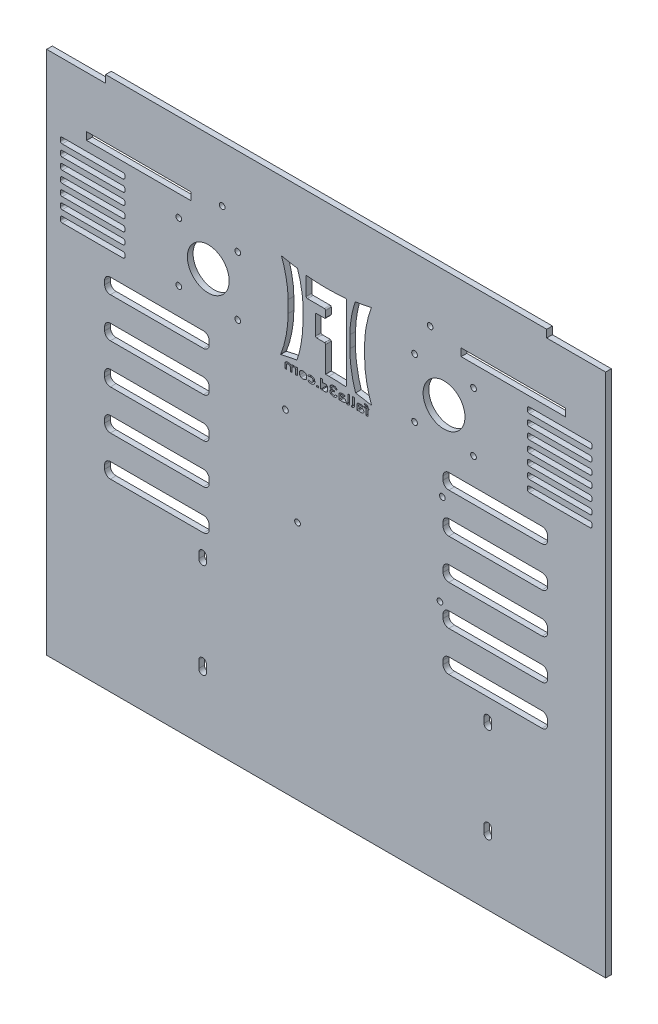
SolidWorks part; units mm, degrees
ref_plane "Front Plane" through (0, 0, 0) normal (0, 0, 1) x (1, 0, 0)
ref_plane "Top Plane" through (0, 0, 0) normal (0, 1, 0) x (1, 0, 0)
ref_plane "Right Plane" through (0, 0, 0) normal (1, 0, 0) x (0, 0, -1)
sketch "Sketch1" plane through (0, 0, 0) normal (0, 0, 1) x (1, 0, 0)
  line L0 (-46.5, 81) -> (-77.5, 81) construction
  line L1 (147, -122) -> (-147, -122)
  line L2 (147, -122) -> (147, 122)
  line L3 (147, 122) -> (-147, 122)
  line L4 (-147, -122) -> (-147, 122)
  line L5 (147, -122) -> (-147, 122) construction
  line L6 (147, 122) -> (-147, -122) construction
  line L7 (-46.5, 81) -> (-46.5, 112) construction
  line L8 (-46.5, 112) -> (-77.5, 112) construction
  line L9 (-77.5, 81) -> (-77.5, 112) construction
  line L10 (-46.5, 81) -> (-77.5, 112) construction
  line L11 (-46.5, 112) -> (-77.5, 81) construction
  line L12 (0, 122) -> (0, -133.2191) construction
  line L13 (46.5, 112) -> (77.5, 81) construction
  line L14 (46.5, 81) -> (77.5, 112) construction
  line L15 (77.5, 81) -> (77.5, 112) construction
  line L16 (46.5, 112) -> (77.5, 112) construction
  line L17 (46.5, 81) -> (46.5, 112) construction
  line L18 (46.5, 81) -> (77.5, 81) construction
  line L19 (-175.5662, 128.75) -> (218.0802, 128.75) construction
  line L20 (-147, 122) -> (147, 122)
  line L21 (-147, 122) -> (-147, 158)
  line L22 (-147, 158) -> (147, 158)
  line L23 (147, 122) -> (147, 158)
  line L24 (0, 158) -> (0, 122) construction
  line L25 (-147, 140) -> (147, 140) construction
  line L26 (147, 156) -> (116, 156) construction
  line L27 (-147, 158) -> (-116, 158)
  line L28 (-147, 158) -> (-147, 154)
  line L29 (-147, 154) -> (-116, 154)
  line L30 (-116, 158) -> (-116, 154)
  line L31 (-131.5, 154) -> (-131.5, 158) construction
  line L32 (-147, 156) -> (-116, 156) construction
  line L33 (131.5, 154) -> (131.5, 158) construction
  line L34 (116, 158) -> (116, 154)
  line L35 (147, 154) -> (116, 154)
  line L36 (147, 158) -> (147, 154)
  line L37 (147, 158) -> (116, 158)
  line L38 (-65, -38) -> (-65, -35.0783) construction
  line L39 (-67, -38) -> (-67, -35.0783)
  line L40 (-63, -38) -> (-63, -35.0783)
  line L41 (-65, -88) -> (-65, -84.0783) construction
  line L42 (-67, -88) -> (-67, -84.0783)
  line L43 (-63, -88) -> (-63, -84.0783)
  line L44 (85, -38) -> (85, -35.0783) construction
  line L45 (83, -38) -> (83, -35.0783)
  line L46 (87, -38) -> (87, -35.0783)
  line L47 (85, -88) -> (85, -84.0783) construction
  line L48 (83, -88) -> (83, -84.0783)
  line L49 (87, -88) -> (87, -84.0783)
  line L50 (-116.5, 63) -> (-61.5, 63) construction
  line L51 (113.5, 67) -> (64.5, 67)
  line L52 (116.5, 64) -> (116.5, 62)
  line L53 (113.5, 59) -> (64.5, 59)
  line L54 (61.5, 64) -> (61.5, 62)
  line L55 (89, 59) -> (89, 67) construction
  line L56 (116.5, 63) -> (61.5, 63) construction
  line L57 (-89, 59) -> (-89, 67) construction
  line L58 (-61.5, 64) -> (-61.5, 62)
  line L59 (-113.5, 59) -> (-64.5, 59)
  line L60 (-116.5, 64) -> (-116.5, 62)
  line L61 (-113.5, 67) -> (-64.5, 67)
  line L62 (113.5, 46) -> (64.5, 46)
  line L63 (116.5, 43) -> (116.5, 41)
  line L64 (113.5, 38) -> (64.5, 38)
  line L65 (61.5, 43) -> (61.5, 41)
  line L66 (-61.5, 43) -> (-61.5, 41)
  line L67 (-113.5, 38) -> (-64.5, 38)
  line L68 (-116.5, 43) -> (-116.5, 41)
  line L69 (-113.5, 46) -> (-64.5, 46)
  line L70 (-116.5, 42) -> (-61.5, 42) construction
  line L71 (89, 38) -> (89, 46) construction
  line L72 (116.5, 42) -> (61.5, 42) construction
  line L73 (-89, 38) -> (-89, 46) construction
  line L74 (113.5, 25) -> (64.5, 25)
  line L75 (116.5, 22) -> (116.5, 20)
  line L76 (113.5, 17) -> (64.5, 17)
  line L77 (61.5, 22) -> (61.5, 20)
  line L78 (-61.5, 22) -> (-61.5, 20)
  line L79 (-113.5, 17) -> (-64.5, 17)
  line L80 (-116.5, 22) -> (-116.5, 20)
  line L81 (-113.5, 25) -> (-64.5, 25)
  line L82 (-116.5, 21) -> (-61.5, 21) construction
  line L83 (89, 17) -> (89, 25) construction
  line L84 (116.5, 21) -> (61.5, 21) construction
  line L85 (-89, 17) -> (-89, 25) construction
  line L86 (113.5, 4) -> (64.5, 4)
  line L87 (116.5, 1) -> (116.5, -1)
  line L88 (113.5, -4) -> (64.5, -4)
  line L89 (61.5, 1) -> (61.5, -1)
  line L90 (-61.5, 1) -> (-61.5, -1)
  line L91 (-113.5, -4) -> (-64.5, -4)
  line L92 (-116.5, 1) -> (-116.5, -1)
  line L93 (-113.5, 4) -> (-64.5, 4)
  line L94 (-116.5, 0) -> (-61.5, 0) construction
  line L95 (89, -4) -> (89, 4) construction
  line L96 (116.5, 0) -> (61.5, 0) construction
  line L97 (-89, -4) -> (-89, 4) construction
  line L98 (113.5, -17) -> (64.5, -17)
  line L99 (116.5, -20) -> (116.5, -22)
  line L100 (113.5, -25) -> (64.5, -25)
  line L101 (61.5, -20) -> (61.5, -22)
  line L102 (-61.5, -20) -> (-61.5, -22)
  line L103 (-113.5, -25) -> (-64.5, -25)
  line L104 (-116.5, -20) -> (-116.5, -22)
  line L105 (-113.5, -17) -> (-64.5, -17)
  line L106 (-116.5, -21) -> (-61.5, -21) construction
  line L107 (89, -25) -> (89, -17) construction
  line L108 (116.5, -21) -> (61.5, -21) construction
  line L109 (-89, -25) -> (-89, -17) construction
  line L110 (0, 79) -> (0, 82) construction
  line L111 (0, 87) -> (0, 90) construction
  line L112 (0, 95) -> (0, 98) construction
  line L113 (0, 111) -> (0, 114) construction
  line L116 (0, 103) -> (0, 106) construction
  line L117 (-15.0972, 71.2645) -> (-15.0972, 74.8635)
  line L118 (-16.0206, 71.2645) -> (-15.0972, 71.2645)
  line L119 (-16.0206, 73.4099) -> (-16.0206, 71.2645)
  line L121 (-17.937, 71.2645) -> (-17.937, 73.4099)
  line L122 (-18.8595, 71.2645) -> (-17.937, 71.2645)
  line L123 (-18.8595, 73.4099) -> (-18.8595, 71.2645)
  line L125 (-20.7714, 71.2645) -> (-20.7714, 73.4099)
  line L126 (-21.6948, 71.2645) -> (-20.7714, 71.2645)
  line L127 (-21.6948, 73.6569) -> (-21.6948, 71.2645)
  line L129 (-16.0215, 74.4822) -> (-16.0391, 74.4822)
  line L130 (-159.7263, 127) -> (156.3882, 127) construction
  line L131 (126, 125) -> (71, 125) construction
  line L132 (-126, 127) -> (-71, 127)
  line L133 (-126, 127) -> (-126, 123)
  line L134 (-126, 123) -> (-71, 123)
  line L135 (-71, 127) -> (-71, 123)
  line L136 (-98.5, 123) -> (-98.5, 127) construction
  line L137 (-126, 125) -> (-71, 125) construction
  line L138 (98.5, 123) -> (98.5, 127) construction
  line L139 (71, 127) -> (71, 123)
  line L140 (126, 123) -> (71, 123)
  line L141 (126, 127) -> (126, 123)
  line L142 (126, 127) -> (71, 127)
  line L143 (57.643, 132.7279) -> (57.643, 166.0775) construction
  line L144 (138.8255, 118) -> (106.8255, 118)
  line L145 (139.8255, 117) -> (139.8255, 116)
  line L146 (138.8255, 115) -> (106.8255, 115)
  line L147 (105.8255, 117) -> (105.8255, 116)
  line L148 (122.8255, 115) -> (122.8255, 118) construction
  line L149 (139.8255, 116.5) -> (105.8255, 116.5) construction
  line L150 (138.8255, 112) -> (106.8255, 112)
  line L151 (139.8255, 111) -> (139.8255, 110)
  line L152 (138.8255, 109) -> (106.8255, 109)
  line L153 (105.8255, 111) -> (105.8255, 110)
  line L154 (122.8255, 109) -> (122.8255, 112) construction
  line L155 (139.8255, 110.5) -> (105.8255, 110.5) construction
  line L156 (138.8255, 106) -> (106.8255, 106)
  line L157 (139.8255, 105) -> (139.8255, 104)
  line L158 (138.8255, 103) -> (106.8255, 103)
  line L159 (105.8255, 105) -> (105.8255, 104)
  line L160 (122.8255, 103) -> (122.8255, 106) construction
  line L161 (139.8255, 104.5) -> (105.8255, 104.5) construction
  line L162 (138.8255, 100) -> (106.8255, 100)
  line L163 (139.8255, 99) -> (139.8255, 98)
  line L164 (138.8255, 97) -> (106.8255, 97)
  line L165 (105.8255, 99) -> (105.8255, 98)
  line L166 (122.8255, 97) -> (122.8255, 100) construction
  line L167 (139.8255, 98.5) -> (105.8255, 98.5) construction
  line L168 (-139.8255, 98.5) -> (-105.8255, 98.5) construction
  line L169 (-122.8255, 97) -> (-122.8255, 100) construction
  line L170 (-139.8255, 104.5) -> (-105.8255, 104.5) construction
  line L171 (-122.8255, 103) -> (-122.8255, 106) construction
  line L172 (-139.8255, 110.5) -> (-105.8255, 110.5) construction
  line L173 (-122.8255, 109) -> (-122.8255, 112) construction
  line L174 (-139.8255, 116.5) -> (-105.8255, 116.5) construction
  line L175 (-122.8255, 115) -> (-122.8255, 118) construction
  line L176 (-105.8255, 99) -> (-105.8255, 98)
  line L177 (-138.8255, 97) -> (-106.8255, 97)
  line L178 (-139.8255, 99) -> (-139.8255, 98)
  line L179 (-138.8255, 100) -> (-106.8255, 100)
  line L180 (-105.8255, 105) -> (-105.8255, 104)
  line L181 (-138.8255, 103) -> (-106.8255, 103)
  line L182 (-139.8255, 105) -> (-139.8255, 104)
  line L183 (-138.8255, 106) -> (-106.8255, 106)
  line L184 (-105.8255, 111) -> (-105.8255, 110)
  line L185 (-138.8255, 109) -> (-106.8255, 109)
  line L186 (-139.8255, 111) -> (-139.8255, 110)
  line L187 (-138.8255, 112) -> (-106.8255, 112)
  line L188 (-105.8255, 117) -> (-105.8255, 116)
  line L189 (-138.8255, 115) -> (-106.8255, 115)
  line L190 (-139.8255, 117) -> (-139.8255, 116)
  line L191 (-138.8255, 118) -> (-106.8255, 118)
  line L192 (138.8255, 94) -> (106.8255, 94)
  line L193 (139.8255, 93) -> (139.8255, 92)
  line L194 (138.8255, 91) -> (106.8255, 91)
  line L195 (105.8255, 93) -> (105.8255, 92)
  line L196 (122.8255, 91) -> (122.8255, 94) construction
  line L197 (139.8255, 92.5) -> (105.8255, 92.5) construction
  line L198 (138.8255, 88) -> (106.8255, 88)
  line L199 (139.8255, 87) -> (139.8255, 86)
  line L200 (138.8255, 85) -> (106.8255, 85)
  line L201 (105.8255, 87) -> (105.8255, 86)
  line L202 (122.8255, 85) -> (122.8255, 88) construction
  line L203 (139.8255, 86.5) -> (105.8255, 86.5) construction
  line L204 (138.8255, 82) -> (106.8255, 82)
  line L205 (139.8255, 81) -> (139.8255, 80)
  line L206 (138.8255, 79) -> (106.8255, 79)
  line L207 (105.8255, 81) -> (105.8255, 80)
  line L208 (122.8255, 79) -> (122.8255, 82) construction
  line L209 (139.8255, 80.5) -> (105.8255, 80.5) construction
  line L210 (-139.8255, 80.5) -> (-105.8255, 80.5) construction
  line L211 (-122.8255, 79) -> (-122.8255, 82) construction
  line L212 (-139.8255, 86.5) -> (-105.8255, 86.5) construction
  line L213 (-122.8255, 85) -> (-122.8255, 88) construction
  line L214 (-139.8255, 92.5) -> (-105.8255, 92.5) construction
  line L215 (-122.8255, 91) -> (-122.8255, 94) construction
  line L216 (-105.8255, 81) -> (-105.8255, 80)
  line L217 (-138.8255, 79) -> (-106.8255, 79)
  line L218 (-139.8255, 81) -> (-139.8255, 80)
  line L219 (-138.8255, 82) -> (-106.8255, 82)
  line L220 (-105.8255, 87) -> (-105.8255, 86)
  line L221 (-138.8255, 85) -> (-106.8255, 85)
  line L222 (-139.8255, 87) -> (-139.8255, 86)
  line L223 (-138.8255, 88) -> (-106.8255, 88)
  line L224 (-105.8255, 93) -> (-105.8255, 92)
  line L225 (-138.8255, 91) -> (-106.8255, 91)
  line L226 (-139.8255, 93) -> (-139.8255, 92)
  line L227 (-138.8255, 94) -> (-106.8255, 94)
  line L312 (-16.0215, 74.8635) -> (-16.0215, 74.4822)
  line L313 (-15.0972, 74.8635) -> (-16.0215, 74.8635)
  line L314 (-8.9982, 72.3195) -> (-9.6805, 71.8437)
  line L315 (-9.6805, 74.2824) -> (-8.9983, 73.8085)
  line L316 (-4.0805, 71.2645) -> (-4.0805, 71.9854)
  line L317 (-5.003, 71.2645) -> (-4.0805, 71.2645)
  line L318 (-5.003, 71.9854) -> (-5.003, 71.2645)
  line L319 (-4.0805, 71.9854) -> (-5.003, 71.9854)
  line L320 (-1.9409, 71.2645) -> (-1.9409, 71.6403)
  line L321 (-2.8636, 71.2645) -> (-1.9409, 71.2645)
  line L322 (-2.8636, 76.3198) -> (-2.8636, 71.2645)
  line L323 (-1.9409, 76.3198) -> (-2.8636, 76.3198)
  line L324 (-1.9409, 74.4844) -> (-1.9409, 76.3198)
  line L325 (4.3101, 73.5498) -> (4.3101, 74.187)
  line L326 (3.915, 73.5498) -> (4.3101, 73.5498)
  line L327 (5.7799, 72.5174) -> (4.8542, 72.5174)
  line L328 (4.8235, 75.027) -> (5.7499, 75.027)
  line L329 (4.3101, 74.187) -> (3.9912, 74.187)
  line L330 (7.5681, 72.5301) -> (7.5681, 72.7904)
  line L331 (7.5681, 72.7904) -> (8.6769, 72.7904)
  line L332 (7.5681, 71.2645) -> (7.5681, 71.5833)
  line L333 (6.6455, 71.2645) -> (7.5681, 71.2645)
  line L334 (6.6455, 73.7227) -> (6.6455, 71.2645)
  line L335 (9.3835, 73.9505) -> (10.1096, 74.3844)
  line L336 (7.5681, 73.386) -> (7.5681, 73.7659)
  line L337 (8.8472, 73.386) -> (7.5681, 73.386)
  line L338 (7.5681, 71.5833) -> (7.5859, 71.5833)
  line L339 (12.3957, 72.1348) -> (12.3957, 76.3198)
  line L340 (10.8071, 71.2645) -> (11.2186, 71.2645)
  line L341 (10.8071, 71.9437) -> (10.8071, 71.2645)
  line L342 (11.1268, 71.9437) -> (10.8071, 71.9437)
  line L343 (11.4731, 76.3198) -> (11.4731, 72.1901)
  line L344 (12.3957, 76.3198) -> (11.4731, 76.3198)
  line L345 (14.8095, 72.1348) -> (14.8095, 76.3198)
  line L346 (13.2209, 71.2645) -> (13.6324, 71.2645)
  line L347 (13.2209, 71.9437) -> (13.2209, 71.2645)
  line L348 (13.5406, 71.9437) -> (13.2209, 71.9437)
  line L349 (13.8869, 76.3198) -> (13.8869, 72.1901)
  line L350 (14.8095, 76.3198) -> (13.8869, 76.3198)
  line L351 (17.0771, 72.5301) -> (17.0771, 72.7904)
  line L352 (17.0771, 72.7904) -> (18.1859, 72.7904)
  line L353 (17.0771, 71.2645) -> (17.0771, 71.5833)
  line L354 (16.1546, 71.2645) -> (17.0771, 71.2645)
  line L355 (16.1546, 73.7227) -> (16.1546, 71.2645)
  line L356 (18.8925, 73.9505) -> (19.6186, 74.3844)
  line L357 (17.0771, 73.386) -> (17.0771, 73.7659)
  line L358 (18.3562, 73.386) -> (17.0771, 73.386)
  line L359 (17.0771, 71.5833) -> (17.0949, 71.5833)
  line L360 (21.9459, 71.2645) -> (21.9459, 74.309)
  line L361 (21.0233, 71.2645) -> (21.9459, 71.2645)
  line L362 (21.0233, 74.309) -> (21.0233, 71.2645)
  line L363 (20.0961, 74.309) -> (21.0233, 74.309)
  line L364 (20.0961, 74.8635) -> (20.0961, 74.309)
  line L365 (21.0233, 74.8635) -> (20.0961, 74.8635)
  line L366 (21.0233, 75.3409) -> (21.0233, 74.8635)
  line L367 (20.0961, 75.6404) -> (20.624, 75.6404)
  line L368 (20.0961, 76.3198) -> (20.0961, 75.6404)
  line L369 (20.6935, 76.3198) -> (20.0961, 76.3198)
  line L370 (21.9459, 74.8635) -> (21.9459, 75.3385)
  line L371 (22.412, 74.8635) -> (21.9459, 74.8635)
  line L372 (22.412, 74.309) -> (22.412, 74.8635)
  line L373 (21.9459, 74.309) -> (22.412, 74.309)
  line L374 (-12.1798, 103.6841) -> (-12.1798, 97.3083)
  line L375 (-19.9834, 97.1434) -> (-19.9834, 103.5191)
  line L376 (10.5734, 119.1124) -> (10.5734, 79.3774)
  line L377 (-10.5308, 109.7145) -> (-10.5308, 119.2775)
  line L378 (-0.913, 109) -> (-9.8167, 109)
  line L379 (-0.3087, 105.0979) -> (-0.3087, 108.3952)
  line L380 (-5.0349, 104.6033) -> (-0.8581, 104.6033)
  line L381 (-5.64, 94.1058) -> (-5.64, 104.0539)
  line L382 (-0.8581, 93.5019) -> (-4.9798, 93.5019)
  line L383 (-0.3087, 79.4322) -> (-0.3087, 92.7869)
  line L384 (20.2456, 103.5191) -> (20.2456, 97.1434)
  line L385 (12.4414, 97.3083) -> (12.4414, 103.6841)
  circle A0 centre (-77.5, 112) radius 1.5
  circle A1 centre (-46.5, 112) radius 1.5
  circle A2 centre (77.5, 81) radius 1.5
  circle A3 centre (-62, 96.5) radius 11
  circle A4 centre (-46.5, 81) radius 1.5
  circle A5 centre (-77.5, 81) radius 1.5
  circle A6 centre (46.5, 81) radius 1.5
  circle A7 centre (62, 96.5) radius 11
  circle A8 centre (46.5, 112) radius 1.5
  circle A9 centre (77.5, 112) radius 1.5
  circle A10 centre (85, -38) radius 2 construction
  circle A11 centre (85, -88) radius 2 construction
  circle A12 centre (-65, -38) radius 2 construction
  circle A13 centre (-65, -88) radius 2 construction
  circle A14 centre (61.1213, 54.1951) radius 1.5
  circle A15 centre (-54.7, 128.75) radius 1.5
  circle A16 centre (-15.0651, 4.4351) radius 1.5
  circle A17 centre (59.8499, 5.9351) radius 1.5
  circle A18 centre (-21.4151, 52.6951) radius 1.5
  circle A19 centre (54.7, 128.75) radius 1.5
  arc A20 (-67, -38) -> (-63, -38) centre (-65, -38) ccw
  arc A21 (-63, -35.0783) -> (-67, -35.0783) centre (-65, -35.0783) ccw
  arc A22 (83, -38) -> (87, -38) centre (85, -38) ccw
  arc A23 (-67, -88) -> (-63, -88) centre (-65, -88) ccw
  arc A24 (-63, -84.0783) -> (-67, -84.0783) centre (-65, -84.0783) ccw
  arc A25 (87, -35.0783) -> (83, -35.0783) centre (85, -35.0783) ccw
  arc A26 (83, -88) -> (87, -88) centre (85, -88) ccw
  arc A27 (87, -84.0783) -> (83, -84.0783) centre (85, -84.0783) ccw
  arc A28 (64.5, 67) -> (61.5, 64) centre (64.5, 64) ccw
  arc A29 (64.5, 59) -> (61.5, 62) centre (64.5, 62) cw
  arc A30 (116.5, 62) -> (113.5, 59) centre (113.5, 62) cw
  arc A31 (113.5, 67) -> (116.5, 64) centre (113.5, 64) cw
  arc A32 (-113.5, 67) -> (-116.5, 64) centre (-113.5, 64) ccw
  arc A33 (-116.5, 62) -> (-113.5, 59) centre (-113.5, 62) ccw
  arc A34 (-64.5, 59) -> (-61.5, 62) centre (-64.5, 62) ccw
  arc A35 (-64.5, 67) -> (-61.5, 64) centre (-64.5, 64) cw
  arc A36 (64.5, 46) -> (61.5, 43) centre (64.5, 43) ccw
  arc A37 (64.5, 38) -> (61.5, 41) centre (64.5, 41) cw
  arc A38 (116.5, 41) -> (113.5, 38) centre (113.5, 41) cw
  arc A39 (113.5, 46) -> (116.5, 43) centre (113.5, 43) cw
  arc A40 (-113.5, 46) -> (-116.5, 43) centre (-113.5, 43) ccw
  arc A41 (-116.5, 41) -> (-113.5, 38) centre (-113.5, 41) ccw
  arc A42 (-64.5, 38) -> (-61.5, 41) centre (-64.5, 41) ccw
  arc A43 (-64.5, 46) -> (-61.5, 43) centre (-64.5, 43) cw
  arc A44 (64.5, 25) -> (61.5, 22) centre (64.5, 22) ccw
  arc A45 (64.5, 17) -> (61.5, 20) centre (64.5, 20) cw
  arc A46 (116.5, 20) -> (113.5, 17) centre (113.5, 20) cw
  arc A47 (113.5, 25) -> (116.5, 22) centre (113.5, 22) cw
  arc A48 (-113.5, 25) -> (-116.5, 22) centre (-113.5, 22) ccw
  arc A49 (-116.5, 20) -> (-113.5, 17) centre (-113.5, 20) ccw
  arc A50 (-64.5, 17) -> (-61.5, 20) centre (-64.5, 20) ccw
  arc A51 (-64.5, 25) -> (-61.5, 22) centre (-64.5, 22) cw
  arc A52 (64.5, 4) -> (61.5, 1) centre (64.5, 1) ccw
  arc A53 (64.5, -4) -> (61.5, -1) centre (64.5, -1) cw
  arc A54 (116.5, -1) -> (113.5, -4) centre (113.5, -1) cw
  arc A55 (113.5, 4) -> (116.5, 1) centre (113.5, 1) cw
  arc A56 (-113.5, 4) -> (-116.5, 1) centre (-113.5, 1) ccw
  arc A57 (-116.5, -1) -> (-113.5, -4) centre (-113.5, -1) ccw
  arc A58 (-64.5, -4) -> (-61.5, -1) centre (-64.5, -1) ccw
  arc A59 (-64.5, 4) -> (-61.5, 1) centre (-64.5, 1) cw
  arc A60 (64.5, -17) -> (61.5, -20) centre (64.5, -20) ccw
  arc A61 (64.5, -25) -> (61.5, -22) centre (64.5, -22) cw
  arc A62 (116.5, -22) -> (113.5, -25) centre (113.5, -22) cw
  arc A63 (113.5, -17) -> (116.5, -20) centre (113.5, -20) cw
  arc A64 (-113.5, -17) -> (-116.5, -20) centre (-113.5, -20) ccw
  arc A65 (-116.5, -22) -> (-113.5, -25) centre (-113.5, -22) ccw
  arc A66 (-64.5, -25) -> (-61.5, -22) centre (-64.5, -22) ccw
  arc A67 (-64.5, -17) -> (-61.5, -20) centre (-64.5, -20) cw
  arc A88 (106.8255, 118) -> (105.8255, 117) centre (106.8255, 117) ccw
  arc A89 (106.8255, 115) -> (105.8255, 116) centre (106.8255, 116) cw
  arc A90 (139.8255, 116) -> (138.8255, 115) centre (138.8255, 116) cw
  arc A91 (138.8255, 118) -> (139.8255, 117) centre (138.8255, 117) cw
  arc A92 (106.8255, 112) -> (105.8255, 111) centre (106.8255, 111) ccw
  arc A93 (106.8255, 109) -> (105.8255, 110) centre (106.8255, 110) cw
  arc A94 (139.8255, 110) -> (138.8255, 109) centre (138.8255, 110) cw
  arc A95 (138.8255, 112) -> (139.8255, 111) centre (138.8255, 111) cw
  arc A96 (106.8255, 106) -> (105.8255, 105) centre (106.8255, 105) ccw
  arc A97 (106.8255, 103) -> (105.8255, 104) centre (106.8255, 104) cw
  arc A98 (139.8255, 104) -> (138.8255, 103) centre (138.8255, 104) cw
  arc A99 (138.8255, 106) -> (139.8255, 105) centre (138.8255, 105) cw
  arc A100 (106.8255, 100) -> (105.8255, 99) centre (106.8255, 99) ccw
  arc A101 (106.8255, 97) -> (105.8255, 98) centre (106.8255, 98) cw
  arc A102 (139.8255, 98) -> (138.8255, 97) centre (138.8255, 98) cw
  arc A103 (138.8255, 100) -> (139.8255, 99) centre (138.8255, 99) cw
  arc A104 (-138.8255, 100) -> (-139.8255, 99) centre (-138.8255, 99) ccw
  arc A105 (-139.8255, 98) -> (-138.8255, 97) centre (-138.8255, 98) ccw
  arc A106 (-106.8255, 97) -> (-105.8255, 98) centre (-106.8255, 98) ccw
  arc A107 (-106.8255, 100) -> (-105.8255, 99) centre (-106.8255, 99) cw
  arc A108 (-138.8255, 106) -> (-139.8255, 105) centre (-138.8255, 105) ccw
  arc A109 (-139.8255, 104) -> (-138.8255, 103) centre (-138.8255, 104) ccw
  arc A110 (-106.8255, 103) -> (-105.8255, 104) centre (-106.8255, 104) ccw
  arc A111 (-106.8255, 106) -> (-105.8255, 105) centre (-106.8255, 105) cw
  arc A112 (-138.8255, 112) -> (-139.8255, 111) centre (-138.8255, 111) ccw
  arc A113 (-139.8255, 110) -> (-138.8255, 109) centre (-138.8255, 110) ccw
  arc A114 (-106.8255, 109) -> (-105.8255, 110) centre (-106.8255, 110) ccw
  arc A115 (-106.8255, 112) -> (-105.8255, 111) centre (-106.8255, 111) cw
  arc A116 (-138.8255, 118) -> (-139.8255, 117) centre (-138.8255, 117) ccw
  arc A117 (-139.8255, 116) -> (-138.8255, 115) centre (-138.8255, 116) ccw
  arc A118 (-106.8255, 115) -> (-105.8255, 116) centre (-106.8255, 116) ccw
  arc A119 (-106.8255, 118) -> (-105.8255, 117) centre (-106.8255, 117) cw
  arc A120 (106.8255, 94) -> (105.8255, 93) centre (106.8255, 93) ccw
  arc A121 (106.8255, 91) -> (105.8255, 92) centre (106.8255, 92) cw
  arc A122 (139.8255, 92) -> (138.8255, 91) centre (138.8255, 92) cw
  arc A123 (138.8255, 94) -> (139.8255, 93) centre (138.8255, 93) cw
  arc A124 (106.8255, 88) -> (105.8255, 87) centre (106.8255, 87) ccw
  arc A125 (106.8255, 85) -> (105.8255, 86) centre (106.8255, 86) cw
  arc A126 (139.8255, 86) -> (138.8255, 85) centre (138.8255, 86) cw
  arc A127 (138.8255, 88) -> (139.8255, 87) centre (138.8255, 87) cw
  arc A128 (106.8255, 82) -> (105.8255, 81) centre (106.8255, 81) ccw
  arc A129 (106.8255, 79) -> (105.8255, 80) centre (106.8255, 80) cw
  arc A130 (139.8255, 80) -> (138.8255, 79) centre (138.8255, 80) cw
  arc A131 (138.8255, 82) -> (139.8255, 81) centre (138.8255, 81) cw
  arc A132 (-138.8255, 82) -> (-139.8255, 81) centre (-138.8255, 81) ccw
  arc A133 (-139.8255, 80) -> (-138.8255, 79) centre (-138.8255, 80) ccw
  arc A134 (-106.8255, 79) -> (-105.8255, 80) centre (-106.8255, 80) ccw
  arc A135 (-106.8255, 82) -> (-105.8255, 81) centre (-106.8255, 81) cw
  arc A136 (-138.8255, 88) -> (-139.8255, 87) centre (-138.8255, 87) ccw
  arc A137 (-139.8255, 86) -> (-138.8255, 85) centre (-138.8255, 86) ccw
  arc A138 (-106.8255, 85) -> (-105.8255, 86) centre (-106.8255, 86) ccw
  arc A139 (-106.8255, 88) -> (-105.8255, 87) centre (-106.8255, 87) cw
  arc A140 (-138.8255, 94) -> (-139.8255, 93) centre (-138.8255, 93) ccw
  arc A141 (-139.8255, 92) -> (-138.8255, 91) centre (-138.8255, 92) ccw
  arc A142 (-106.8255, 91) -> (-105.8255, 92) centre (-106.8255, 92) ccw
  arc A143 (-106.8255, 94) -> (-105.8255, 93) centre (-106.8255, 93) cw
  spline S172 degree 3 poles (-16.2997, 73.9864) (-16.1136, 73.8544) (-16.0206, 73.6622) (-16.0206, 73.4099) knots 22 22 22 22 23 23 23 23
  spline S173 degree 3 poles (-16.9835, 74.1878) (-16.7044, 74.1878) (-16.4763, 74.1205) (-16.2997, 73.9864) knots 21 21 21 21 22 22 22 22
  spline S174 degree 3 poles (-17.6719, 73.9864) (-17.492, 74.1205) (-17.2625, 74.1878) (-16.9835, 74.1878) knots 20 20 20 20 21 21 21 21
  spline S175 degree 3 poles (-17.937, 73.4099) (-17.937, 73.6622) (-17.8485, 73.8544) (-17.6719, 73.9864) knots 19 19 19 19 20 20 20 20
  spline S176 degree 3 poles (-19.1341, 73.9864) (-18.951, 73.8544) (-18.8595, 73.6622) (-18.8595, 73.4099) knots 15 15 15 15 16 16 16 16
  spline S177 degree 3 poles (-19.8224, 74.1878) (-19.5433, 74.1878) (-19.314, 74.1205) (-19.1341, 73.9864) knots 14 14 14 14 15 15 15 15
  spline S178 degree 3 poles (-20.5062, 73.9864) (-20.3294, 74.1205) (-20.1016, 74.1878) (-19.8224, 74.1878) knots 13 13 13 13 14 14 14 14
  spline S179 degree 3 poles (-20.7714, 73.4099) (-20.7714, 73.6622) (-20.683, 73.8544) (-20.5062, 73.9864) knots 12 12 12 12 13 13 13 13
  spline S180 degree 3 poles (-21.1918, 74.593) (-21.5151, 74.3804) (-21.6826, 74.0683) (-21.6948, 73.6569) knots 8 8 8 8 9 9 9 9
  spline S181 degree 3 poles (-20.113, 74.9085) (-20.506, 74.9085) (-20.8658, 74.8034) (-21.1918, 74.593) knots 7 7 7 7 8 8 8 8
  spline S182 degree 3 poles (-18.6179, 74.4369) (-18.9896, 74.756) (-19.488, 74.9131) (-20.113, 74.9085) knots 6 6 6 6 7 7 7 7
  spline S183 degree 3 poles (-18.0738, 74.7802) (-18.2719, 74.6902) (-18.4532, 74.5757) (-18.6179, 74.4369) knots 5 5 5 5 6 6 6 6
  spline S184 degree 3 poles (-17.2783, 74.9085) (-17.6074, 74.9039) (-17.8725, 74.8611) (-18.0738, 74.7802) knots 4 4 4 4 5 5 5 5
  spline S185 degree 3 poles (-16.0391, 74.4822) (-16.3532, 74.7664) (-16.7661, 74.9085) (-17.2783, 74.9085) knots 3 3 3 3 4 4 4 4
  spline S186 degree 3 poles (-13.0911, 73.0606) (-13.0911, 73.318) (-13.0764, 73.5058) (-13.0468, 73.6242) knots 0 0 0 0 1 1 1 1
  spline S187 degree 3 poles (-13.0468, 73.6242) (-13.017, 73.7377) (-12.9564, 73.8375) (-12.8647, 73.9233) knots 1 1 1 1 2 2 2 2
  spline S188 degree 3 poles (-12.8647, 73.9233) (-12.7967, 74.0044) (-12.6962, 74.0682) (-12.5629, 74.1146) knots 2 2 2 2 3 3 3 3
  spline S189 degree 3 poles (-12.5629, 74.1146) (-12.4358, 74.1633) (-12.2877, 74.1878) (-12.1192, 74.1878) (-11.9622, 74.1878) (-11.8174, 74.1633) (-11.6842, 74.1146) knots 3 3 3 3 4 4 4 5 5 5 5
  spline S190 degree 3 poles (-11.6842, 74.1146) (-11.557, 74.0682) (-11.4536, 74.0044) (-11.3736, 73.9233) knots 5 5 5 5 6 6 6 6
  spline S191 degree 3 poles (-11.3736, 73.9233) (-11.2937, 73.8375) (-11.236, 73.7377) (-11.2005, 73.6242) knots 6 6 6 6 7 7 7 7
  spline S192 degree 3 poles (-11.2005, 73.6242) (-11.1651, 73.5058) (-11.1472, 73.3202) (-11.1472, 73.0674) (-11.1472, 72.8169) (-11.1651, 72.6337) (-11.2005, 72.5177) knots 7 7 7 7 8 8 8 9 9 9 9
  spline S193 degree 3 poles (-11.2005, 72.5177) (-11.236, 72.3994) (-11.2937, 72.2952) (-11.3736, 72.2046) knots 9 9 9 9 10 10 10 10
  spline S194 degree 3 poles (-11.3736, 72.2046) (-11.4536, 72.1352) (-11.557, 72.0736) (-11.6842, 72.0203) knots 10 10 10 10 11 11 11 11
  spline S195 degree 3 poles (-11.6842, 72.0203) (-11.8174, 71.9692) (-11.9622, 71.9437) (-12.1192, 71.9437) (-12.2877, 71.9437) (-12.4358, 71.9692) (-12.5629, 72.0203) knots 11 11 11 11 12 12 12 13 13 13 13
  spline S196 degree 3 poles (-12.5629, 72.0203) (-12.6962, 72.0736) (-12.7967, 72.1352) (-12.8647, 72.2046) knots 13 13 13 13 14 14 14 14
  spline S197 degree 3 poles (-12.8647, 72.2046) (-12.9564, 72.2952) (-13.017, 72.3994) (-13.0468, 72.5177) knots 14 14 14 14 15 15 15 15
  spline S198 degree 3 poles (-13.0468, 72.5177) (-13.0764, 72.6337) (-13.0911, 72.8147) (-13.0911, 73.0606) knots 15 15 15 15 16 16 16 16
  spline S199 degree 3 poles (-10.2246, 73.0674) (-10.2246, 73.4472) (-10.2644, 73.739) (-10.3442, 73.9428) knots 0 0 0 0 1 1 1 1
  spline S200 degree 3 poles (-10.3442, 73.9428) (-10.4269, 74.1418) (-10.5539, 74.3098) (-10.725, 74.4463) knots 1 1 1 1 2 2 2 2
  spline S201 degree 3 poles (-10.725, 74.4463) (-10.8519, 74.566) (-11.0291, 74.6729) (-11.2564, 74.7672) knots 2 2 2 2 3 3 3 3
  spline S202 degree 3 poles (-11.2564, 74.7672) (-11.4808, 74.8569) (-11.7687, 74.9039) (-12.1199, 74.9085) knots 3 3 3 3 4 4 4 4
  spline S203 degree 3 poles (-12.1199, 74.9085) (-12.483, 74.9039) (-12.7768, 74.8565) (-13.0012, 74.7664) knots 4 4 4 4 5 5 5 5
  spline S204 degree 3 poles (-13.0012, 74.7664) (-13.2227, 74.6716) (-13.3937, 74.5641) (-13.5148, 74.4439) knots 5 5 5 5 6 6 6 6
  spline S205 degree 3 poles (-13.5148, 74.4439) (-13.6973, 74.3076) (-13.8267, 74.14) (-13.9033, 73.9412) knots 6 6 6 6 7 7 7 7
  spline S206 degree 3 poles (-13.9033, 73.9412) (-13.977, 73.7377) (-14.0137, 73.4465) (-14.0137, 73.0674) (-14.0137, 72.6883) (-13.9768, 72.3994) (-13.9031, 72.2006) knots 7 7 7 7 8 8 8 9 9 9 9
  spline S207 degree 3 poles (-13.9031, 72.2006) (-13.8263, 72.0017) (-13.6964, 71.8296) (-13.5135, 71.684) knots 9 9 9 9 10 10 10 10
  spline S208 degree 3 poles (-13.5135, 71.684) (-13.4544, 71.6309) (-13.3821, 71.5789) (-13.2965, 71.528) knots 10 10 10 10 11 11 11 11
  spline S209 degree 3 poles (-13.2965, 71.528) (-13.2199, 71.4701) (-13.121, 71.4205) (-12.9999, 71.379) knots 11 11 11 11 12 12 12 12
  spline S210 degree 3 poles (-12.9999, 71.379) (-12.7757, 71.2796) (-12.4821, 71.2276) (-12.1192, 71.223) knots 12 12 12 12 13 13 13 13
  spline S211 degree 3 poles (-12.1192, 71.223) (-11.768, 71.2276) (-11.4802, 71.2796) (-11.256, 71.379) knots 13 13 13 13 14 14 14 14
  spline S212 degree 3 poles (-11.256, 71.379) (-11.0287, 71.469) (-10.8517, 71.5708) (-10.7248, 71.684) knots 14 14 14 14 15 15 15 15
  spline S213 degree 3 poles (-10.7248, 71.684) (-10.5537, 71.8296) (-10.4267, 72.0017) (-10.3442, 72.2006) knots 15 15 15 15 16 16 16 16
  spline S214 degree 3 poles (-10.3442, 72.2006) (-10.2644, 72.3994) (-10.2246, 72.6883) (-10.2246, 73.0674) knots 16 16 16 16 17 17 17 17
  spline S215 degree 3 poles (-8.0639, 71.9437) (-8.4535, 71.9483) (-8.765, 72.0736) (-8.9982, 72.3195) knots 12 12 12 12 13 13 13 13
  spline S216 degree 3 poles (-6.8682, 73.0606) (-6.8801, 72.3044) (-7.2785, 71.9321) (-8.0639, 71.9437) knots 11 11 11 11 12 12 12 12
  spline S217 degree 3 poles (-8.0639, 74.1878) (-7.2787, 74.197) (-6.8801, 73.8212) (-6.8682, 73.0606) knots 10 10 10 10 11 11 11 11
  spline S218 degree 3 poles (-8.9983, 73.8085) (-8.7651, 74.052) (-8.4537, 74.1784) (-8.0639, 74.1878) knots 9 9 9 9 10 10 10 10
  spline S219 degree 3 poles (-8.9724, 74.7356) (-9.2438, 74.6226) (-9.4798, 74.4715) (-9.6805, 74.2824) knots 7 7 7 7 8 8 8 8
  spline S220 degree 3 poles (-8.0297, 74.9085) (-8.3868, 74.9039) (-8.7008, 74.8462) (-8.9724, 74.7356) knots 6 6 6 6 7 7 7 7
  spline S221 degree 3 poles (-6.6006, 74.4822) (-7.0106, 74.771) (-7.4871, 74.9131) (-8.0297, 74.9085) knots 5 5 5 5 6 6 6 6
  spline S222 degree 3 poles (-5.9457, 73.0606) (-5.9575, 73.7146) (-6.1758, 74.1885) (-6.6006, 74.4822) knots 4 4 4 4 5 5 5 5
  spline S223 degree 3 poles (-6.5999, 71.6563) (-6.1756, 71.9451) (-5.9575, 72.4134) (-5.9457, 73.0606) knots 3 3 3 3 4 4 4 4
  spline S224 degree 3 poles (-8.0281, 71.223) (-7.4858, 71.223) (-7.0097, 71.3674) (-6.5999, 71.6563) knots 2 2 2 2 3 3 3 3
  spline S225 degree 3 poles (-8.9715, 71.4056) (-8.6999, 71.2884) (-8.3853, 71.2276) (-8.0281, 71.223) knots 1 1 1 1 2 2 2 2
  spline S226 degree 3 poles (-9.6805, 71.8437) (-9.4796, 71.6644) (-9.2433, 71.5183) (-8.9715, 71.4056) knots 0 0 0 0 1 1 1 1
  spline S227 degree 3 poles (-1.0328, 74.1878) (-0.8143, 74.1878) (-0.6475, 74.1587) (-0.5324, 74.1007) knots 0 0 0 0 1 1 1 1
  spline S228 degree 3 poles (-0.5324, 74.1007) (-0.4054, 74.0382) (-0.3123, 73.9524) (-0.2532, 73.8432) knots 1 1 1 1 2 2 2 2
  spline S229 degree 3 poles (-0.2532, 73.8432) (-0.1971, 73.7343) (-0.1602, 73.6159) (-0.1425, 73.4884) knots 2 2 2 2 3 3 3 3
  spline S230 degree 3 poles (-0.1425, 73.4884) (-0.1249, 73.3515) (-0.1159, 73.2113) (-0.1159, 73.0674) (-0.1159, 72.9307) (-0.1249, 72.7973) (-0.1425, 72.6673) knots 3 3 3 3 4 4 4 5 5 5 5
  spline S231 degree 3 poles (-0.1425, 72.6673) (-0.1602, 72.5304) (-0.1971, 72.4077) (-0.2532, 72.2985) knots 5 5 5 5 6 6 6 6
  spline S232 degree 3 poles (-0.2532, 72.2985) (-0.3123, 72.1941) (-0.4054, 72.1083) (-0.5324, 72.0411) knots 6 6 6 6 7 7 7 7
  spline S233 degree 3 poles (-0.5324, 72.0411) (-0.6475, 71.9762) (-0.8143, 71.9437) (-1.0328, 71.9437) (-1.2514, 71.9437) (-1.4241, 71.9786) (-1.5511, 72.0481) knots 7 7 7 7 8 8 8 9 9 9 9
  spline S234 degree 3 poles (-1.5511, 72.0481) (-1.6781, 72.1153) (-1.7652, 72.2035) (-1.8124, 72.3125) knots 9 9 9 9 10 10 10 10
  spline S235 degree 3 poles (-1.8124, 72.3125) (-1.8715, 72.4215) (-1.9113, 72.5433) (-1.9321, 72.6778) knots 10 10 10 10 11 11 11 11
  spline S236 degree 3 poles (-1.9321, 72.6778) (-1.9379, 72.8099) (-1.9409, 72.9399) (-1.9409, 73.0674) (-1.9409, 73.2065) (-1.9379, 73.3399) (-1.9321, 73.4676) knots 11 11 11 11 12 12 12 13 13 13 13
  spline S237 degree 3 poles (-1.9321, 73.4676) (-1.9113, 73.5951) (-1.8715, 73.7133) (-1.8124, 73.8225) knots 13 13 13 13 14 14 14 14
  spline S238 degree 3 poles (-1.8124, 73.8225) (-1.7652, 73.9314) (-1.6781, 74.0195) (-1.5511, 74.0869) knots 14 14 14 14 15 15 15 15
  spline S239 degree 3 poles (-1.5511, 74.0869) (-1.4241, 74.154) (-1.2514, 74.1878) (-1.0328, 74.1878) knots 15 15 15 15 16 16 16 16
  spline S240 degree 3 poles (-1.4055, 74.7947) (-1.5914, 74.7143) (-1.7698, 74.6108) (-1.9409, 74.4844) knots 9 9 9 9 10 10 10 10
  spline S241 degree 3 poles (-0.7507, 74.9085) (-0.9867, 74.9085) (-1.2049, 74.8706) (-1.4055, 74.7947) knots 8 8 8 8 9 9 9 9
  spline S242 degree 3 poles (0.4793, 74.4395) (0.2197, 74.7407) (-0.1903, 74.8971) (-0.7507, 74.9085) knots 7 7 7 7 8 8 8 8
  spline S243 degree 3 poles (0.7315, 73.9919) (0.6901, 74.1769) (0.6061, 74.3262) (0.4793, 74.4395) knots 6 6 6 6 7 7 7 7
  spline S244 degree 3 poles (0.8066, 73.0688) (0.8066, 73.5014) (0.7815, 73.809) (0.7315, 73.9919) knots 5 5 5 5 6 6 6 6
  spline S245 degree 3 poles (0.7315, 72.1528) (0.7815, 72.3379) (0.8066, 72.6433) (0.8066, 73.0688) knots 4 4 4 4 5 5 5 5
  spline S246 degree 3 poles (0.4793, 71.6914) (0.6061, 71.8048) (0.6901, 71.9586) (0.7315, 72.1528) knots 3 3 3 3 4 4 4 4
  spline S247 degree 3 poles (-0.0384, 71.3582) (0.1681, 71.4415) (0.3406, 71.5526) (0.4793, 71.6914) knots 2 2 2 2 3 3 3 3
  spline S248 degree 3 poles (-0.7507, 71.223) (-0.4734, 71.2276) (-0.2359, 71.2726) (-0.0384, 71.3582) knots 1 1 1 1 2 2 2 2
  spline S249 degree 3 poles (-1.9409, 71.6403) (-1.637, 71.3711) (-1.2403, 71.2322) (-0.7507, 71.223) knots 0 0 0 0 1 1 1 1
  spline S250 degree 3 poles (3.2064, 73.3447) (3.3925, 73.4814) (3.6286, 73.5498) (3.915, 73.5498) knots 26 26 26 26 27 27 27 27
  spline S251 degree 3 poles (2.9143, 72.7467) (2.9201, 73.004) (3.0175, 73.2032) (3.2064, 73.3447) knots 25 25 25 25 26 26 26 26
  spline S252 degree 3 poles (3.2065, 72.1627) (3.0175, 72.2994) (2.9201, 72.494) (2.9143, 72.7467) knots 24 24 24 24 25 25 25 25
  spline S253 degree 3 poles (3.8931, 71.9437) (3.6215, 71.9437) (3.3926, 72.0166) (3.2065, 72.1627) knots 23 23 23 23 24 24 24 24
  spline S254 degree 3 poles (4.5043, 72.1072) (4.3508, 71.9983) (4.147, 71.9437) (3.8931, 71.9437) knots 22 22 22 22 23 23 23 23
  spline S255 degree 3 poles (4.8542, 72.5174) (4.7716, 72.3481) (4.655, 72.2114) (4.5043, 72.1072) knots 21 21 21 21 22 22 22 22
  spline S256 degree 3 poles (5.1205, 71.5552) (5.4598, 71.7766) (5.6796, 72.0973) (5.7799, 72.5174) knots 19 19 19 19 20 20 20 20
  spline S257 degree 3 poles (3.9522, 71.223) (4.3918, 71.223) (4.7813, 71.3336) (5.1205, 71.5552) knots 18 18 18 18 19 19 19 19
  spline S258 degree 3 poles (2.5536, 71.6493) (2.9166, 71.3696) (3.3828, 71.2276) (3.9522, 71.223) knots 17 17 17 17 18 18 18 18
  spline S259 degree 3 poles (1.9916, 72.7693) (1.9976, 72.2954) (2.1849, 71.922) (2.5536, 71.6493) knots 16 16 16 16 17 17 17 17
  spline S260 degree 3 poles (2.1699, 73.3794) (2.0511, 73.1854) (1.9916, 72.9819) (1.9916, 72.7693) knots 15 15 15 15 16 16 16 16
  spline S261 degree 3 poles (2.7779, 73.8787) (2.4976, 73.7401) (2.2949, 73.5736) (2.1699, 73.3794) knots 14 14 14 14 15 15 15 15
  spline S262 degree 3 poles (2.2065, 74.3607) (2.3132, 74.1804) (2.5037, 74.0198) (2.7779, 73.8787) knots 13 13 13 13 14 14 14 14
  spline S263 degree 3 poles (2.0693, 74.9224) (2.0693, 74.7282) (2.1151, 74.541) (2.2065, 74.3607) knots 12 12 12 12 13 13 13 13
  spline S264 degree 3 poles (2.5742, 75.921) (2.2435, 75.6389) (2.0752, 75.3062) (2.0693, 74.9224) knots 11 11 11 11 12 12 12 12
  spline S265 degree 3 poles (3.9738, 76.3613) (3.3863, 76.3567) (2.9197, 76.2099) (2.5742, 75.921) knots 10 10 10 10 11 11 11 11
  spline S266 degree 3 poles (5.1697, 75.9732) (4.8361, 76.2273) (4.4375, 76.3567) (3.9738, 76.3613) knots 9 9 9 9 10 10 10 10
  spline S267 degree 3 poles (5.7499, 75.027) (5.7027, 75.4013) (5.5093, 75.7167) (5.1697, 75.9732) knots 8 8 8 8 9 9 9 9
  spline S268 degree 3 poles (4.4777, 75.4906) (4.6492, 75.3907) (4.7644, 75.2361) (4.8235, 75.027) knots 6 6 6 6 7 7 7 7
  spline S269 degree 3 poles (3.9369, 75.6404) (4.1349, 75.6404) (4.3152, 75.5904) (4.4777, 75.4906) knots 5 5 5 5 6 6 6 6
  spline S270 degree 3 poles (3.2631, 75.4348) (3.4375, 75.5673) (3.6621, 75.6358) (3.9369, 75.6404) knots 4 4 4 4 5 5 5 5
  spline S271 degree 3 poles (2.9928, 74.9085) (2.9987, 75.1222) (3.0888, 75.2977) (3.2631, 75.4348) knots 3 3 3 3 4 4 4 4
  spline S272 degree 3 poles (3.2546, 74.3927) (3.0801, 74.5252) (2.9928, 74.697) (2.9928, 74.9085) knots 2 2 2 2 3 3 3 3
  spline S273 degree 3 poles (3.9912, 74.187) (3.6747, 74.187) (3.4292, 74.2556) (3.2546, 74.3927) knots 1 1 1 1 2 2 2 2
  spline S274 degree 3 poles (7.7855, 72.0096) (7.6406, 72.0861) (7.5681, 72.2596) (7.5681, 72.5301) knots 5 5 5 5 6 6 6 6
  spline S275 degree 3 poles (8.606, 71.9021) (8.2187, 71.8976) (7.9452, 71.9334) (7.7855, 72.0096) knots 4 4 4 4 5 5 5 5
  spline S276 degree 3 poles (9.2669, 72.0444) (9.1339, 71.9496) (8.9135, 71.9021) (8.606, 71.9021) knots 3 3 3 3 4 4 4 4
  spline S277 degree 3 poles (9.4754, 72.3566) (9.4754, 72.234) (9.4059, 72.13) (9.2669, 72.0444) knots 2 2 2 2 3 3 3 3
  spline S278 degree 3 poles (8.6769, 72.7904) (9.2154, 72.7811) (9.4815, 72.6365) (9.4754, 72.3566) knots 1 1 1 1 2 2 2 2
  spline S279 degree 3 poles (7.1719, 74.652) (6.8269, 74.4717) (6.6514, 74.1619) (6.6455, 73.7227) knots 15 15 15 15 16 16 16 16
  spline S280 degree 3 poles (8.5568, 74.9085) (7.9787, 74.9131) (7.5171, 74.8276) (7.1719, 74.652) knots 14 14 14 14 15 15 15 15
  spline S281 degree 3 poles (10.1096, 74.3844) (9.7587, 74.7431) (9.2411, 74.9177) (8.5568, 74.9085) knots 13 13 13 13 14 14 14 14
  spline S282 degree 3 poles (9.0559, 74.1736) (9.1946, 74.1293) (9.3038, 74.0551) (9.3835, 73.9505) knots 11 11 11 11 12 12 12 12
  spline S283 degree 3 poles (8.5113, 74.2293) (8.7415, 74.2293) (8.923, 74.2107) (9.0559, 74.1736) knots 10 10 10 10 11 11 11 11
  spline S284 degree 3 poles (7.5681, 73.7659) (7.5621, 74.0841) (7.8764, 74.2385) (8.5113, 74.2293) knots 9 9 9 9 10 10 10 10
  spline S285 degree 3 poles (9.9625, 73.0742) (9.7088, 73.2774) (9.337, 73.3814) (8.8472, 73.386) knots 6 6 6 6 7 7 7 7
  spline S286 degree 3 poles (10.3431, 72.3219) (10.3431, 72.6245) (10.2162, 72.8753) (9.9625, 73.0742) knots 5 5 5 5 6 6 6 6
  spline S287 degree 3 poles (9.9049, 71.5418) (10.1971, 71.7452) (10.3431, 72.0052) (10.3431, 72.3219) knots 4 4 4 4 5 5 5 5
  spline S288 degree 3 poles (8.7188, 71.223) (9.2323, 71.2276) (9.6276, 71.3338) (9.9049, 71.5418) knots 3 3 3 3 4 4 4 4
  spline S289 degree 3 poles (7.9842, 71.313) (8.1612, 71.2529) (8.4061, 71.223) (8.7188, 71.223) knots 2 2 2 2 3 3 3 3
  spline S290 degree 3 poles (7.5859, 71.5833) (7.6714, 71.4609) (7.8042, 71.3707) (7.9842, 71.313) knots 1 1 1 1 2 2 2 2
  spline S291 degree 3 poles (12.0506, 71.4613) (12.2808, 71.5949) (12.3957, 71.8193) (12.3957, 72.1348) knots 7 7 7 7 8 8 8 8
  spline S292 degree 3 poles (11.2186, 71.2645) (11.555, 71.2645) (11.8323, 71.3301) (12.0506, 71.4613) knots 6 6 6 6 7 7 7 7
  spline S293 degree 3 poles (11.4731, 72.1901) (11.4731, 72.0258) (11.3577, 71.9437) (11.1268, 71.9437) knots 2 2 2 2 3 3 3 3
  spline S294 degree 3 poles (14.4644, 71.4613) (14.6946, 71.5949) (14.8095, 71.8193) (14.8095, 72.1348) knots 7 7 7 7 8 8 8 8
  spline S295 degree 3 poles (13.6324, 71.2645) (13.9688, 71.2645) (14.2461, 71.3301) (14.4644, 71.4613) knots 6 6 6 6 7 7 7 7
  spline S296 degree 3 poles (13.8869, 72.1901) (13.8869, 72.0258) (13.7715, 71.9437) (13.5406, 71.9437) knots 2 2 2 2 3 3 3 3
  spline S297 degree 3 poles (17.2945, 72.0096) (17.1496, 72.0861) (17.0771, 72.2596) (17.0771, 72.5301) knots 5 5 5 5 6 6 6 6
  spline S298 degree 3 poles (18.115, 71.9021) (17.7277, 71.8976) (17.4542, 71.9334) (17.2945, 72.0096) knots 4 4 4 4 5 5 5 5
  spline S299 degree 3 poles (18.7759, 72.0444) (18.6429, 71.9496) (18.4225, 71.9021) (18.115, 71.9021) knots 3 3 3 3 4 4 4 4
  spline S300 degree 3 poles (18.9844, 72.3566) (18.9844, 72.234) (18.9149, 72.13) (18.7759, 72.0444) knots 2 2 2 2 3 3 3 3
  spline S301 degree 3 poles (18.1859, 72.7904) (18.7244, 72.7811) (18.9906, 72.6365) (18.9844, 72.3566) knots 1 1 1 1 2 2 2 2
  spline S302 degree 3 poles (16.681, 74.652) (16.3359, 74.4717) (16.1604, 74.1619) (16.1546, 73.7227) knots 15 15 15 15 16 16 16 16
  spline S303 degree 3 poles (18.0658, 74.9085) (17.4877, 74.9131) (17.0261, 74.8276) (16.681, 74.652) knots 14 14 14 14 15 15 15 15
  spline S304 degree 3 poles (19.6186, 74.3844) (19.2677, 74.7431) (18.7501, 74.9177) (18.0658, 74.9085) knots 13 13 13 13 14 14 14 14
  spline S305 degree 3 poles (18.5649, 74.1736) (18.7036, 74.1293) (18.8128, 74.0551) (18.8925, 73.9505) knots 11 11 11 11 12 12 12 12
  spline S306 degree 3 poles (18.0203, 74.2293) (18.2505, 74.2293) (18.432, 74.2107) (18.5649, 74.1736) knots 10 10 10 10 11 11 11 11
  spline S307 degree 3 poles (17.0771, 73.7659) (17.0711, 74.0841) (17.3854, 74.2385) (18.0203, 74.2293) knots 9 9 9 9 10 10 10 10
  spline S308 degree 3 poles (19.4715, 73.0742) (19.2178, 73.2774) (18.846, 73.3814) (18.3562, 73.386) knots 6 6 6 6 7 7 7 7
  spline S309 degree 3 poles (19.8521, 72.3219) (19.8521, 72.6245) (19.7252, 72.8753) (19.4715, 73.0742) knots 5 5 5 5 6 6 6 6
  spline S310 degree 3 poles (19.4139, 71.5418) (19.7061, 71.7452) (19.8521, 72.0052) (19.8521, 72.3219) knots 4 4 4 4 5 5 5 5
  spline S311 degree 3 poles (18.2279, 71.223) (18.7413, 71.2276) (19.1366, 71.3338) (19.4139, 71.5418) knots 3 3 3 3 4 4 4 4
  spline S312 degree 3 poles (17.4932, 71.313) (17.6702, 71.2529) (17.9151, 71.223) (18.2279, 71.223) knots 2 2 2 2 3 3 3 3
  spline S313 degree 3 poles (17.0949, 71.5833) (17.1804, 71.4609) (17.3132, 71.3707) (17.4932, 71.313) knots 1 1 1 1 2 2 2 2
  spline S314 degree 3 poles (20.624, 75.6404) (20.9024, 75.6474) (21.0355, 75.5474) (21.0233, 75.3409) knots 9 9 9 9 10 10 10 10
  spline S315 degree 3 poles (21.583, 76.0943) (21.347, 76.2446) (21.0505, 76.3198) (20.6935, 76.3198) knots 5 5 5 5 6 6 6 6
  spline S316 degree 3 poles (21.9459, 75.3385) (21.9459, 75.6805) (21.825, 75.9326) (21.583, 76.0943) knots 4 4 4 4 5 5 5 5
  spline S317 degree 3 poles (-23.9395, 76.4974) (-23.9395, 76.5931) (-23.9367, 76.6511) (-23.8858, 76.7543) knots 8 8 8 8 9 9 9 9
  spline S318 degree 3 poles (-15.338, 78.2737) (-18.247, 77.7996) (-21.1169, 77.2076) (-23.9395, 76.4974) knots 7 7 7 7 8 8 8 8
  spline S319 degree 3 poles (-12.1798, 97.3083) (-12.1798, 90.0013) (-13.9381, 81.9389) (-15.338, 78.2737) knots 6 6 6 6 7 7 7 7
  spline S320 degree 3 poles (-15.063, 120.154) (-13.6778, 116.4219) (-12.1798, 109.5626) (-12.1798, 103.6841) knots 4 4 4 4 5 5 5 5
  spline S321 degree 3 poles (-23.5717, 121.7624) (-20.7775, 121.111) (-17.9384, 120.5753) (-15.063, 120.154) knots 3 3 3 3 4 4 4 4
  spline S322 degree 3 poles (-19.9834, 103.5191) (-19.9834, 109.2201) (-21.5276, 116.6085) (-23.5717, 121.7624) knots 2 2 2 2 3 3 3 3
  spline S323 degree 3 poles (-23.8858, 76.7543) (-21.8523, 81.4805) (-19.9834, 89.615) (-19.9834, 97.1434) knots 0 0 0 0 1 1 1 1
  spline S324 degree 3 poles (1.5048, 79.3492) (0.9037, 79.3492) (0.3061, 79.3371) (-0.2925, 79.3265) knots 21 21 21 21 22 22 22 22
  spline S325 degree 3 poles (10.4302, 78.9642) (7.4874, 79.2144) (4.5121, 79.3492) (1.5048, 79.3492) knots 20 20 20 20 21 21 21 21
  spline S326 degree 3 poles (10.5734, 79.3774) (10.5734, 79.2217) (10.5117, 79.0833) (10.4302, 78.9642) knots 19 19 19 19 20 20 20 20
  spline S327 degree 3 poles (10.5455, 119.2732) (10.5562, 119.2198) (10.5734, 119.1671) (10.5734, 119.1124) knots 17 17 17 17 18 18 18 18
  spline S328 degree 3 poles (0.1308, 118.7556) (3.6463, 118.7556) (7.1199, 118.9323) (10.5455, 119.2732) knots 16 16 16 16 17 17 17 17
  spline S329 degree 3 poles (-10.5272, 119.2956) (-7.0233, 118.9388) (-3.4677, 118.7556) (0.1308, 118.7556) knots 15 15 15 15 16 16 16 16
  spline S330 degree 3 poles (-10.5308, 119.2775) (-10.5308, 119.2838) (-10.5272, 119.2893) (-10.5272, 119.2956) knots 14 14 14 14 15 15 15 15
  spline S331 degree 3 poles (-9.8167, 109) (-10.2013, 109) (-10.5308, 109.3298) (-10.5308, 109.7145) knots 12 12 12 12 13 13 13 13
  spline S332 degree 3 poles (-0.3087, 108.3952) (-0.3087, 108.78) (-0.5829, 109) (-0.913, 109) knots 10 10 10 10 11 11 11 11
  spline S333 degree 3 poles (-0.8581, 104.6033) (-0.473, 104.6033) (-0.3087, 104.8233) (-0.3087, 105.0979) knots 8 8 8 8 9 9 9 9
  spline S334 degree 3 poles (-5.64, 104.0539) (-5.64, 104.3284) (-5.3101, 104.6033) (-5.0349, 104.6033) knots 6 6 6 6 7 7 7 7
  spline S335 degree 3 poles (-4.9798, 93.5019) (-5.3649, 93.5019) (-5.64, 93.7762) (-5.64, 94.1058) knots 4 4 4 4 5 5 5 5
  spline S336 degree 3 poles (-0.3087, 92.7869) (-0.3087, 93.1169) (-0.5829, 93.5019) (-0.8581, 93.5019) knots 2 2 2 2 3 3 3 3
  spline S337 degree 3 poles (-0.2925, 79.3265) (-0.2962, 79.364) (-0.3087, 79.3922) (-0.3087, 79.4322) knots 0 0 0 0 1 1 1 1
  spline S338 degree 3 poles (15.4654, 78.703) (14.0988, 82.5418) (12.4414, 90.2749) (12.4414, 97.3083) knots 7 7 7 7 8 8 8 8
  spline S339 degree 3 poles (23.9656, 77.1983) (21.1724, 77.814) (18.3381, 78.3173) (15.4654, 78.703) knots 6 6 6 6 7 7 7 7
  spline S340 degree 3 poles (20.2456, 97.1434) (20.2456, 89.8405) (22.0043, 81.9777) (23.9656, 77.1983) knots 5 5 5 5 6 6 6 6
  spline S341 degree 3 poles (23.8127, 121.7574) (21.779, 116.5588) (20.2456, 109.2006) (20.2456, 103.5191) knots 3 3 3 3 4 4 4 4
  spline S342 degree 3 poles (15.3247, 120.154) (18.1934, 120.5744) (21.0252, 121.108) (23.8127, 121.7574) knots 2 2 2 2 3 3 3 3
  spline S343 degree 3 poles (12.4414, 103.6841) (12.4414, 109.5626) (13.9401, 116.4219) (15.3247, 120.154) knots 1 1 1 1 2 2 2 2
  point P0 (0, 0)
  point P63 (131.5, 156)
  point P65 (-65, -36.5392)
  point P73 (-65, -86.0392)
  point P79 (85, -36.5392)
  point P86 (85, -86.0392)
  point P119 (-89, 63)
  point P132 (-131.5, 156)
  point P154 (-89, 42)
  point P159 (89, 42)
  point P164 (89, 63)
  point P193 (-89, 21)
  point P198 (89, 21)
  point P227 (-89, 0)
  point P232 (89, 0)
  point P261 (-89, -21)
  point P266 (89, -21)
  point P274 (0, 140)
  point P293 (0, 103.5)
  point P306 (0, 95.5)
  point P319 (0, 87.5)
  point P332 (0, 79.5)
  point P345 (98.5, 125)
  point P364 (122.8255, 116.5)
  point P384 (122.8255, 110.5)
  point P401 (122.8255, 104.5)
  point P418 (122.8255, 98.5)
  point P483 (-122.8255, 98.5)
  point P484 (-122.8255, 104.5)
  point P485 (-122.8255, 110.5)
  point P486 (-122.8255, 116.5)
  point P503 (122.8255, 92.5)
  point P520 (122.8255, 86.5)
  point P537 (122.8255, 80.5)
  point P552 (-98.5, 125)
  point P591 (-122.8255, 80.5)
  point P592 (-122.8255, 86.5)
  point P593 (-122.8255, 92.5)
  dimension "D3" = 22
  dimension "D5" = 3
  dimension "D6" = 85
  dimension "D8" = 3
  dimension "D9" = 3
  dimension "D10" = 3
  dimension "D11" = 2
  dimension "D12" = 2
  dimension "D13" = 2
  dimension "D14" = 2
  dimension "D19" = 3
  dimension "D20" = 3
  dimension "D21" = 3
  dimension "D22" = 3
  dimension "D31" = 3
  dimension "D35" = 2
  dimension "D38" = 3
  dimension "D52" = 1
  dimension "D1" = 294
  dimension "D2" = 244
  dimension "D4" = 31
  dimension "D7" = 10
  dimension "D15" = 82
  dimension "D16" = 150
  dimension "D17" = 50
  dimension "D18" = 34
  dimension "D23" = 82.55
  dimension "D24" = 48.26
  dimension "D25" = 74.93
  dimension "D26" = 48.26
  dimension "D28" = 85.8787
  dimension "D29" = 127
  dimension "D30" = 6.75
  dimension "D32" = 54.7
  dimension "D33" = 31
  dimension "D34" = 4
  dimension "D36" = 55
  dimension "D37" = 8
  dimension "D39" = 89
  dimension "D40" = 55
  dimension "D47" = 36
  dimension "D48" = 4
  dimension "D49" = 55
  dimension "D50" = 21
  dimension "D51" = 34
  dimension "D53" = 3
  dimension "D54" = 34
  dimension "D55" = 34
  dimension "D56" = 34
  dimension "D57" = 3
  dimension "D58" = 3
  dimension "D59" = 3
  dimension "D60" = 3
  dimension "D61" = 3
  dimension "D62" = 3
  dimension "D63" = 5
  dimension "D64" = 34
  dimension "D65" = 34
  dimension "D66" = 34
  dimension "D67" = 3
  dimension "D68" = 3
  dimension "D69" = 3
  dimension "D70" = 3
  dimension "D71" = 3
  dimension "D72" = 3
  dimension "D41" = 5
extrude "Boss-Extrude1" add sketch "Sketch1" along normal blind 3 contours L4 L1 L2 L3 A18 A17 A16 A14 A13 A12 A11 A10 A8 A6 A5 A4 A3 A0 A1 A2 A7 A9 | L3 L23 L22 L21 region at (-0.0507, -6.8667, 0) region at (0, 140.2824, 0)
